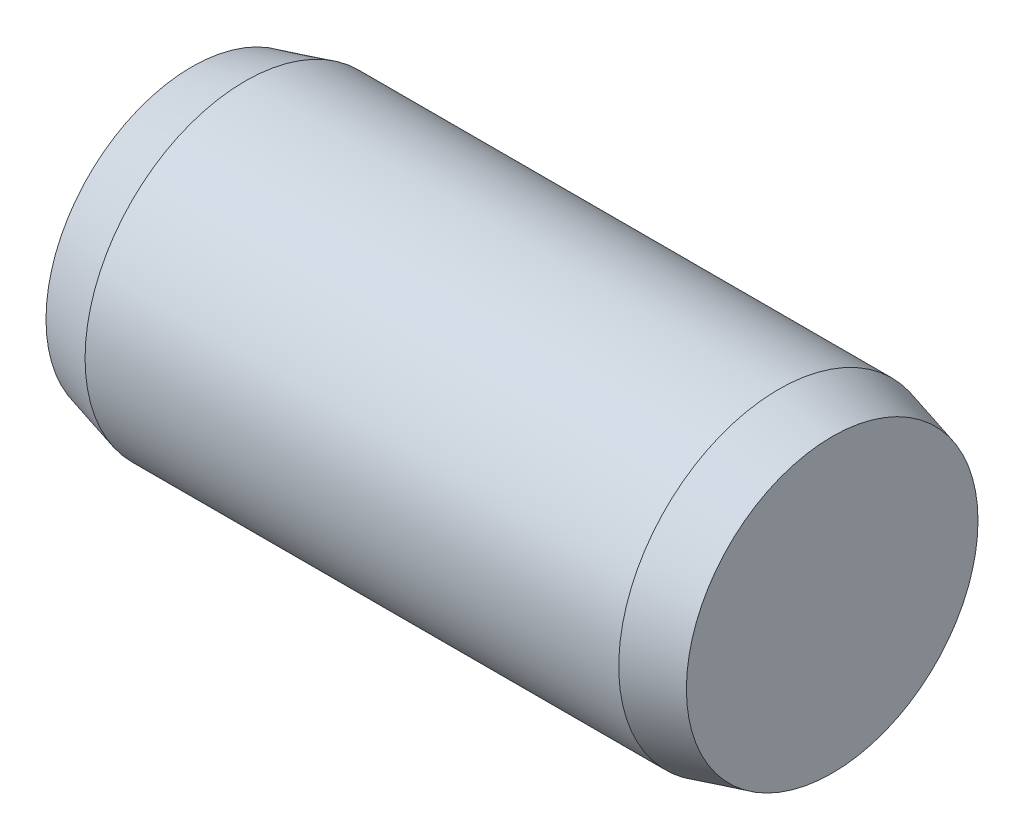
SolidWorks part; units mm, degrees
ref_plane "Front Plane" through (0, 0, 0) normal (0, 0, 1) x (1, 0, 0)
ref_plane "Top Plane" through (0, 0, 0) normal (0, 1, 0) x (1, 0, 0)
ref_plane "Right Plane" through (0, 0, 0) normal (1, 0, 0) x (0, 0, -1)
sketch "Sketch1" plane through (0, 0, 0) normal (0, 0, 1) x (1, 0, 0)
  line L0 (-2.5, 0) -> (2.5, 0) construction
  line L1 (2.5, 1.5) -> (2.5, -1.5) construction
  line L2 (-2.5, 1.5) -> (-2.5, -1.5) construction
  line L3 (3, 1.5) -> (3, -1.5) construction
  line L4 (-3, 1.5) -> (-3, -1.5) construction
  line L5 (-2.5, 0) -> (-3, 0) construction
  line L6 (2.5, 0) -> (3, 0) construction
  dimension "D1" = 0.5
  dimension "Dia" = 3
  dimension "Length" = 6
  dimension "C" = 0.5
sketch "Sketch2" plane through (0, 0, 0) normal (1, 0, 0) x (0, 0, -1)
  circle A0 centre (0, 0) radius 1.5
extrude "Extrude1" add sketch "Sketch2" against normal up to vertex (2.5 mm away) and the other way up to vertex (2.5 mm away) up to point (-2.5, 1.5, 0) other way up to point (2.5, 1.5, 0)
sketch "Sketch3" plane through (2.5, 0, 0) normal (1, 0, 0) x (0, 0, -1)
  circle A1 centre (0, 0) radius 1.5
  circle A2 centre (0, 0) radius 1.5
  dimension "D1" = 0
extrude "Extrude2" add sketch "Sketch3" along normal up to vertex (0.5 mm away) draft 15 up to point (3, 0, 0)
sketch "Sketch4" plane through (-2.5, 0, 0) normal (-1, 0, 0) x (0, 0, 1)
  circle A1 centre (0, 0) radius 1.5
  circle A2 centre (0, 0) radius 1.5
  dimension "D1" = 0
extrude "Extrude3" add sketch "Sketch4" along normal up to vertex (0.5 mm away) draft 15 up to point (-3, 0, 0)
equation "\"D1@Sketch1\" = \"C@Sketch1\""
